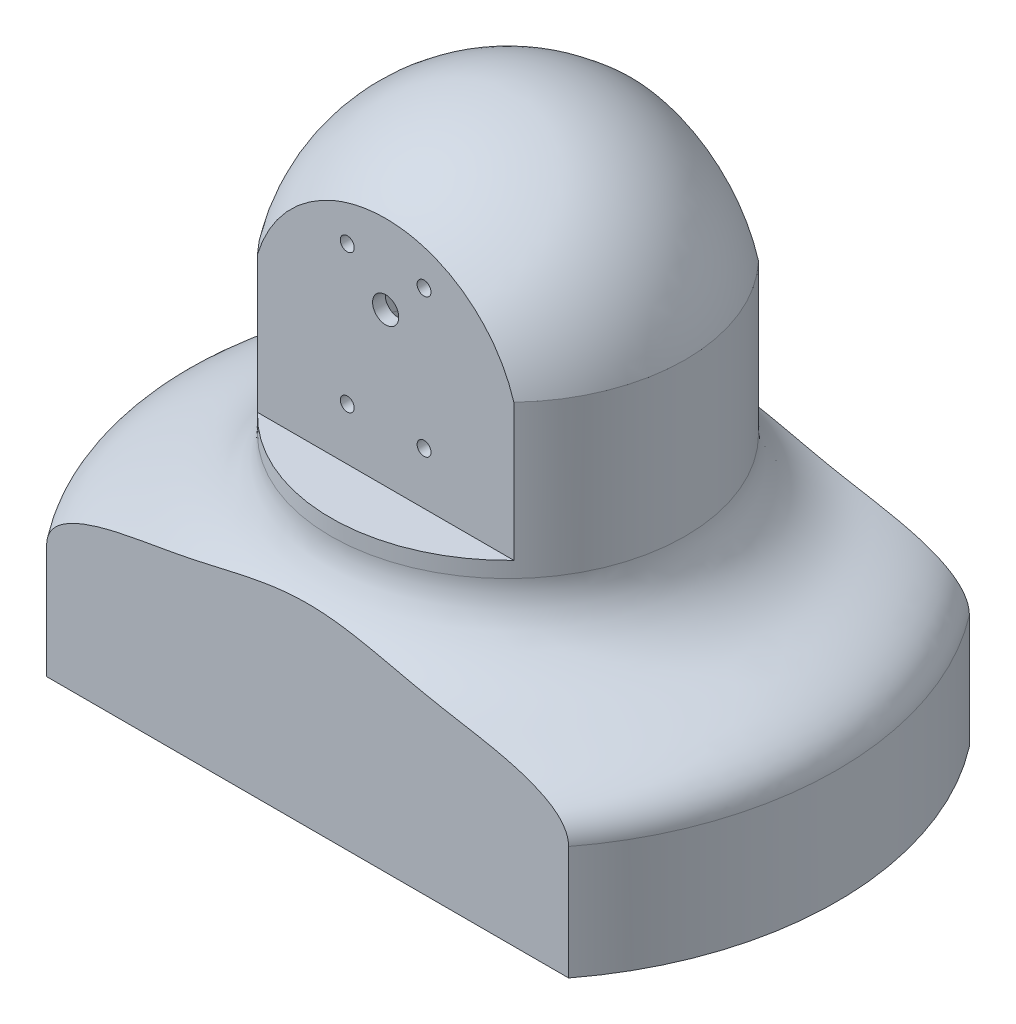
SolidWorks part; units mm, degrees
ref_plane "前视基准面" through (0, 0, 0) normal (0, 0, 1) x (1, 0, 0)
ref_plane "上视基准面" through (0, 0, 0) normal (0, 1, 0) x (1, 0, 0)
ref_plane "右视基准面" through (0, 0, 0) normal (1, 0, 0) x (0, 0, -1)
sketch "草图1" plane through (0, 0, 0) normal (0, 0, 1) x (1, 0, 0)
  line L0 (0, 0) -> (0, 70) construction
  line L2 (42, 36.2195) -> (42, 0)
  line L10 (78, -30) -> (78, -57)
  line L11 (40.3, 36.0333) -> (40.3, 0)
  line L12 (76.3, -30) -> (76.3, -57)
  line L13 (0, 70) -> (0, 68.3)
  line L14 (76.3, -57) -> (78, -57)
  arc A0 (0, 70) -> (42, 36.2195) centre (0, 27) cw
  arc A3 (0, 68.3) -> (40.3, 36.0333) centre (0, 27) cw
  spline S0 degree 3 poles (78, -30) (78, -23.3742) (65.6712, -18.6568) (51.2973, -15.3356) (42, -7.2858) (42, 0) knots 0 0 0 0 0.385389 0.593507 1 1 1 1
  spline S1 degree 1 poles (76.3, -30) (40.3, 0) knots 0 0 1 1 construction
  spline S2 degree 3 poles (40.3, 0) (40.3, -0.6228) (40.3823, -1.8829) (40.851, -4.2563) (41.9515, -7.0083) (43.9043, -9.9015) (47.1183, -13.2234) (50.9478, -15.7672) (54.8412, -17.519) (58.657, -18.8118) (63.4973, -20.0659) (68.9371, -21.9357) (72.5722, -23.9487) (74.3303, -25.4159) (75.3332, -26.6912) (75.8783, -27.6978) (76.1608, -28.599) (76.2792, -29.3716) (76.3, -29.7932) (76.3, -30) knots 0 0 0 0 0.03125 0.0625 0.125 0.1875 0.25 0.375 0.4375 0.5 0.625 0.75 0.8125 0.875 0.90625 0.9375 0.96875 0.984375 1 1 1 1
  point P10 (33.3, -0.85)
  point P11 (73.98, -31.36)
  dimension "D3" = 43
  dimension "D1" = 70
  dimension "D2" = 42
  dimension "D5" = 78
  dimension "D6" = 30
  dimension "D7" = 27
  dimension "D4" = 1.7
revolve "旋转1" add sketch "草图1" angle 360 about L0
sketch "草图6" plane through (0, 0, 0) normal (1, 0, 0) x (0, 0, -1)
  line L0 (42, 0) -> (42, 36.2195) construction
  line L1 (42, 3.749) -> (29, 3.749)
  line L2 (42, 3.749) -> (42, 58.749)
  line L3 (42, 58.749) -> (29, 58.749)
  line L4 (29, 3.749) -> (29, 58.749)
  line L5 (0, 0) -> (0, 35.0449) construction
  line L6 (-42, 58.749) -> (-29, 58.749)
  line L7 (-29, 3.749) -> (-29, 58.749)
  line L8 (-42, 3.749) -> (-29, 3.749)
  line L9 (-42, 3.749) -> (-42, 58.749)
  arc A0 (42, 36.2195) -> (-42, 36.2195) centre (0, 27) ccw construction
  dimension "D1" = 29
  dimension "D2" = 55
extrude "切除-拉伸3" cut sketch "草图6" against normal through all and the other way through all
sketch "草图7" plane through (0, 0, -29) normal (0, 0, -1) x (-1, 0, 0)
  line L0 (30.3809, 3.749) -> (30.3809, 36.2195) construction
  line L1 (-30.3809, 36.2195) -> (-30.3809, 3.749) construction
  line L2 (30.3809, 3.749) -> (30.3809, 36.2195)
  line L3 (-30.3809, 36.2195) -> (-30.3809, 3.749)
  line L4 (-30.3809, 3.749) -> (30.3809, 3.749)
  arc A0 (30.3809, 36.2195) -> (-30.3809, 36.2195) centre (0, 27) ccw construction
  arc A1 (30.3809, 36.2195) -> (-30.3809, 36.2195) centre (0, 27) ccw
extrude "凸台-拉伸3" add sketch "草图7" against normal blind 3 draft 24 draft outward yes
sketch "草图8" plane through (0, 3.749, 0) normal (0, 1, 0) x (1, 0, 0)
  line L1 (-32.9848, 26) -> (32.9848, 26)
  line L4 (-30.7911, 26) -> (30.7911, 26) construction
  arc A0 (30.3809, 29) -> (-30.3809, 29) centre (0, 0) ccw construction
  arc A1 (32.9848, 26) -> (-32.9848, 26) centre (0, 0) ccw
  arc A2 (-30.3809, 29) -> (-30.3809, -29) centre (0, 0) ccw construction
extrude "凸台-拉伸5" add sketch "草图8" against normal blind 2
mirror "镜向1" about plane through (0, 0, 0) normal (0, 0, 1) of "凸台-拉伸5", "凸台-拉伸3"
sketch "草图2" plane through (0, 0, 26) normal (0, 0, 1) x (1, 0, 0)
  line L1 (-9.1, 49) -> (9.1, 49) construction
  line L2 (-9.1, 49) -> (-9.1, 16.1) construction
  line L3 (-9.1, 16.1) -> (9.1, 16.1) construction
  line L4 (9.1, 49) -> (9.1, 16.1) construction
  line L5 (-16, 54.87) -> (16, 54.87) construction
  line L6 (-16, 54.87) -> (-16, 8.87) construction
  line L7 (-16, 8.87) -> (16, 8.87) construction
  line L8 (16, 54.87) -> (16, 8.87) construction
  circle A0 centre (0, 40) radius 3.1
  circle A6 centre (9.1, 49) radius 1.65
  circle A7 centre (-9.1, 49) radius 1.65
  circle A8 centre (-9.1, 16.1) radius 1.65
  circle A9 centre (9.1, 16.1) radius 1.65
  arc A10 (42, 36.2195) -> (-42, 36.2195) centre (0, 27) ccw construction
  point P6 (0, 54.87)
  point P7 (0, 49)
  dimension "D3" = 6.2
  dimension "D8" = 30
  dimension "D9" = 3.3
  dimension "D1" = 32.9
  dimension "D2" = 18.2
  dimension "D4" = 32
  dimension "D5" = 46
  dimension "D6" = 7.23
  dimension "D7" = 9
extrude "切除-拉伸4" cut sketch "草图2" along normal through all
sketch "草图9" plane through (0, 0, -29) normal (0, 0, 1) x (1, 0, 0)
  circle A2 centre (0, 40) radius 4.05
  dimension "D1" = 8.1
extrude "切除-拉伸6" cut sketch "草图9" along normal up to surface (3 mm away) up to face at (0, 24.655, -26)
sketch "草图12" plane through (0, 0, 0) normal (0, 1, 0) x (1, 0, 0)
  line L1 (-61.8688, 47.5) -> (61.8688, 47.5)
  line L2 (-61.8688, 47.5) -> (-61.8688, 80)
  line L3 (-61.8688, 80) -> (61.8688, 80)
  line L4 (61.8688, 47.5) -> (61.8688, 80)
  circle A0 centre (0, 0) radius 78 construction
  dimension "D2" = 2
  dimension "D1" = 47.5
extrude "切除-拉伸7" cut sketch "草图12" against normal through all
sketch "草图13" plane through (0, 0, -47.5) normal (0, 0, -1) x (-1, 0, 0)
  line L0 (-61.8688, -57) -> (-61.8688, -30) construction
  line L1 (61.8688, -57) -> (61.8688, -30) construction
  line L2 (-61.8688, -57) -> (-61.8688, -30)
  line L3 (61.8688, -57) -> (61.8688, -30)
  line L4 (-61.8688, -57) -> (61.8688, -57)
  spline S0 degree 3 poles (1061.8524, -30.5387) (-757.4661, -291.558) (81.6142, -84.0195) (61.269, -27.2442) (60.9178, -26.6293) (60.0514, -25.4965) (59.5514, -24.9967) (58.4724, -24.0909) (57.8871, -23.6815) (56.6856, -22.9434) (56.0678, -22.6129) (54.8091, -22.0047) (54.168, -21.7273) (52.2188, -20.9536) (50.8829, -20.5144) (48.1818, -19.7315) (46.8207, -19.3896) (44.0859, -18.7665) (42.7119, -18.4857) (38.5792, -17.6953) (35.8099, -17.2355) (31.6698, -16.4801) (30.2919, -16.2179) (27.5426, -15.6633) (26.1712, -15.3708) (22.0634, -14.462) (19.3329, -13.8181) (13.8519, -12.6254) (11.0985, -12.0769) (6.9689, -11.4896) (5.5915, -11.3332) (2.8346, -11.12) (1.4551, -11.0635) (-1.3064, -11.0596) (-2.6883, -11.1122) (-5.4544, -11.3193) (-6.8385, -11.4735) (-9.6085, -11.8628) (-10.9964, -12.098) (-13.7611, -12.6197) (-15.1382, -12.9058) (-19.262, -13.8017) (-22.0012, -14.4478) (-26.1217, -15.3601) (-27.4973, -15.6539) (-30.2547, -16.2107) (-31.6366, -16.4739) (-35.7886, -17.2319) (-38.5656, -17.6927) (-42.7111, -18.4855) (-44.0894, -18.7672) (-46.834, -19.3928) (-48.1988, -19.7359) (-50.9001, -20.5198) (-52.2411, -20.9612) (-54.1961, -21.739) (-54.8385, -22.0179) (-56.0986, -22.6288) (-56.7164, -22.9607) (-57.6161, -23.5158) (-57.9123, -23.7112) (-58.4873, -24.1215) (-58.7665, -24.3367) (-59.3048, -24.791) (-59.5639, -25.0302) (-60.0572, -25.5384) (-60.2897, -25.8062) (-60.7136, -26.3645) (-60.9062, -26.6561) (-61.1611, -27.1154) (-61.2404, -27.2722) (-61.3866, -27.5936) (-61.4539, -27.7593) (-84.3344, -91.9368) (1007.071, -362.5093) (-1061.7077, -47.2272) knots -1.287115 -1.287115 -1.287115 -1.287115 0.015625 0.015625 0.03125 0.03125 0.046875 0.046875 0.0625 0.0625 0.078125 0.078125 0.09375 0.09375 0.125 0.125 0.15625 0.15625 0.1875 0.1875 0.25 0.25 0.28125 0.28125 0.3125 0.3125 0.375 0.375 0.4375 0.4375 0.46875 0.46875 0.5 0.5 0.53125 0.53125 0.5625 0.5625 0.59375 0.59375 0.625 0.625 0.6875 0.6875 0.71875 0.71875 0.75 0.75 0.8125 0.8125 0.84375 0.84375 0.875 0.875 0.90625 0.90625 0.921875 0.921875 0.9375 0.9375 0.945312 0.945312 0.953125 0.953125 0.960937 0.960937 0.96875 0.96875 0.976562 0.976562 0.980469 0.980469 0.984375 0.984375 2.479572 2.479572 2.479572 2.479572 only from (61.8688, -30) to (-61.8688, -30) construction
  spline S1 degree 3 poles (61.8688, -30) (61.8688, -29.2846) (61.7513, -28.5899) (61.269, -27.2442) (60.9178, -26.6293) (60.0514, -25.4965) (59.5514, -24.9967) (58.4724, -24.0909) (57.8871, -23.6815) (56.6856, -22.9434) (56.0678, -22.6129) (54.8091, -22.0047) (54.168, -21.7273) (52.2188, -20.9536) (50.8829, -20.5144) (48.1818, -19.7315) (46.8207, -19.3896) (44.0859, -18.7665) (42.7119, -18.4857) (38.5792, -17.6953) (35.8099, -17.2355) (31.6698, -16.4801) (30.2919, -16.2179) (27.5426, -15.6633) (26.1712, -15.3708) (22.0634, -14.462) (19.3329, -13.8181) (13.8519, -12.6254) (11.0985, -12.0769) (6.9689, -11.4896) (5.5915, -11.3332) (2.8346, -11.12) (1.4551, -11.0635) (-1.3064, -11.0596) (-2.6883, -11.1122) (-5.4544, -11.3193) (-6.8385, -11.4735) (-9.6085, -11.8628) (-10.9964, -12.098) (-13.7611, -12.6197) (-15.1382, -12.9058) (-19.262, -13.8017) (-22.0012, -14.4478) (-26.1217, -15.3601) (-27.4973, -15.6539) (-30.2547, -16.2107) (-31.6366, -16.4739) (-35.7886, -17.2319) (-38.5656, -17.6927) (-42.7111, -18.4855) (-44.0894, -18.7672) (-46.834, -19.3928) (-48.1988, -19.7359) (-50.9001, -20.5198) (-52.2411, -20.9612) (-54.1961, -21.739) (-54.8385, -22.0179) (-56.0986, -22.6288) (-56.7164, -22.9607) (-57.6161, -23.5158) (-57.9123, -23.7112) (-58.4873, -24.1215) (-58.7665, -24.3367) (-59.3048, -24.791) (-59.5639, -25.0302) (-60.0572, -25.5384) (-60.2897, -25.8062) (-60.7136, -26.3645) (-60.9062, -26.6561) (-61.1611, -27.1154) (-61.2404, -27.2722) (-61.3866, -27.5936) (-61.4539, -27.7593) (-61.752, -28.5954) (-61.8688, -29.2869) (-61.8688, -30) knots 0 0 0 0 0.015625 0.015625 0.03125 0.03125 0.046875 0.046875 0.0625 0.0625 0.078125 0.078125 0.09375 0.09375 0.125 0.125 0.15625 0.15625 0.1875 0.1875 0.25 0.25 0.28125 0.28125 0.3125 0.3125 0.375 0.375 0.4375 0.4375 0.46875 0.46875 0.5 0.5 0.53125 0.53125 0.5625 0.5625 0.59375 0.59375 0.625 0.625 0.6875 0.6875 0.71875 0.71875 0.75 0.75 0.8125 0.8125 0.84375 0.84375 0.875 0.875 0.90625 0.90625 0.921875 0.921875 0.9375 0.9375 0.945312 0.945312 0.953125 0.953125 0.960937 0.960937 0.96875 0.96875 0.976562 0.976562 0.980469 0.980469 0.984375 0.984375 1 1 1 1
extrude "凸台-拉伸7" add sketch "草图13" against normal blind 2
mirror "镜向2" about plane through (0, 0, 0) normal (0, 0, 1) of "凸台-拉伸7", "切除-拉伸7"
ref_plane "基准面2" through (0, -52, 0) normal (0, -1, 0) x (-1, 0, 0)
sketch "草图14" plane through (0, -52, 0) normal (0, -1, 0) x (1, 0, 0)
  line L0 (0, 0) -> (0, -19.9006) construction
  line L1 (0, 0) -> (17.2749, 0) construction
  line L2 (-61.249, 45.5) -> (61.249, 45.5) construction
  circle A0 centre (-63, 28.5) radius 1.65
  arc A1 (-61.249, 45.5) -> (-61.249, -45.5) centre (0, 0) ccw construction
  arc A2 (-64.5837, 40.628) -> (-73.1545, 21.6821) centre (0, 0) ccw
  arc A3 (-64.5837, 40.628) -> (-61.6777, 32.8013) centre (-60.1325, 37.8279) ccw
  arc A4 (-61.6777, 32.8013) -> (-65.3576, 24.667) centre (-63, 28.5) cw
  arc A5 (-65.3576, 24.667) -> (-73.1545, 21.6821) centre (-68.1126, 20.1878) ccw
  circle A6 centre (-63, -28.5) radius 1.65
  arc A7 (-64.5837, -40.628) -> (-61.6777, -32.8013) centre (-60.1325, -37.8279) cw
  arc A8 (-61.6777, -32.8013) -> (-65.3576, -24.667) centre (-63, -28.5) ccw
  arc A9 (-65.3576, -24.667) -> (-73.1545, -21.6821) centre (-68.1126, -20.1878) cw
  arc A10 (-64.5837, -40.628) -> (-73.1545, -21.6821) centre (0, 0) cw
  arc A11 (64.5837, 40.628) -> (61.6777, 32.8013) centre (60.1325, 37.8279) cw
  arc A12 (61.6777, 32.8013) -> (65.3576, 24.667) centre (63, 28.5) ccw
  arc A13 (65.3576, 24.667) -> (73.1545, 21.6821) centre (68.1126, 20.1878) cw
  arc A14 (64.5837, 40.628) -> (73.1545, 21.6821) centre (0, 0) cw
  circle A15 centre (63, 28.5) radius 1.65
  circle A16 centre (63, -28.5) radius 1.65
  arc A17 (64.5837, -40.628) -> (73.1545, -21.6821) centre (0, 0) ccw
  arc A18 (65.3576, -24.667) -> (73.1545, -21.6821) centre (68.1126, -20.1878) ccw
  arc A19 (61.6777, -32.8013) -> (65.3576, -24.667) centre (63, -28.5) cw
  arc A20 (64.5837, -40.628) -> (61.6777, -32.8013) centre (60.1325, -37.8279) ccw
  dimension "D1" = 4.5
  dimension "D2" = 3.3
  dimension "D3" = 63
  dimension "D5" = 5.2587
  dimension "D4" = 17
extrude "凸台-拉伸8" add sketch "草图14" against normal blind 5
chamfer "倒角1" distance 3 angle 45 4 edges at (69.5175, -47, 31.4484) (69.5175, -47, -31.4484) (-69.5175, -47, 31.4484) (-69.5175, -47, -31.4484)
sketch "草图15" plane through (0, -47, 0) normal (0, 1, 0) x (1, 0, 0)
  line L1 (-61.3834, -31.3) -> (-59.7668, -28.5)
  line L2 (-59.7668, -28.5) -> (-61.3834, -25.7)
  line L3 (-61.3834, -25.7) -> (-64.6166, -25.7)
  line L4 (-64.6166, -25.7) -> (-66.2332, -28.5)
  line L5 (-66.2332, -28.5) -> (-64.6166, -31.3)
  line L6 (-64.6166, -31.3) -> (-61.3834, -31.3)
  line L7 (-64.6166, 25.7) -> (-61.3834, 25.7)
  line L8 (-61.3834, 25.7) -> (-59.7668, 28.5)
  line L9 (-59.7668, 28.5) -> (-61.3834, 31.3)
  line L10 (-61.3834, 31.3) -> (-64.6166, 31.3)
  line L11 (-64.6166, 31.3) -> (-66.2332, 28.5)
  line L12 (-66.2332, 28.5) -> (-64.6166, 25.7)
  line L13 (64.6166, 25.7) -> (66.2332, 28.5)
  line L14 (66.2332, 28.5) -> (64.6166, 31.3)
  line L15 (64.6166, 31.3) -> (61.3834, 31.3)
  line L16 (61.3834, 31.3) -> (59.7668, 28.5)
  line L17 (59.7668, 28.5) -> (61.3834, 25.7)
  line L18 (61.3834, 25.7) -> (64.6166, 25.7)
  line L19 (64.6166, -31.3) -> (66.2332, -28.5)
  line L20 (66.2332, -28.5) -> (64.6166, -25.7)
  line L21 (64.6166, -25.7) -> (61.3834, -25.7)
  line L22 (61.3834, -25.7) -> (59.7668, -28.5)
  line L23 (59.7668, -28.5) -> (61.3834, -31.3)
  line L24 (61.3834, -31.3) -> (64.6166, -31.3)
  circle A0 centre (-63, -28.5) radius 2.8 construction
  circle A1 centre (-63, 28.5) radius 2.8 construction
  circle A2 centre (63, 28.5) radius 2.8 construction
  circle A3 centre (63, -28.5) radius 2.8 construction
  dimension "D1" = 5.6
extrude "切除-拉伸8" cut sketch "草图15" against normal blind 1
sketch "草图18" plane through (0, 3.749, 0) normal (0, 1, 0) x (1, 0, 0)
  line L0 (-30.3809, 29) -> (30.3809, 29)
  line L1 (-29.3939, 30) -> (29.3939, 30)
  circle A0 centre (0, 0) radius 42 construction
  arc A1 (30.3809, 29) -> (29.3939, 30) centre (0, 0) ccw
  arc A2 (-29.3939, 30) -> (-30.3809, 29) centre (0, 0) ccw
  dimension "D1" = 1
extrude "凸台-拉伸10" add sketch "草图18" along normal blind 17
sketch "草图19" plane through (0, 0, -30) normal (0, 0, -1) x (-1, 0, 0)
  line L0 (-22.3809, 15.749) -> (-12.8809, 15.749) construction
  line L1 (0, 0) -> (0, 27.9735) construction
  line L2 (-29.3939, 3.749) -> (29.3939, 3.749) construction
  line L3 (-30.3809, 36.2195) -> (-30.3809, 20.749) construction
  circle A0 centre (-12.8809, 15.749) radius 1.15
  circle A1 centre (-22.3809, 15.749) radius 1.15
  circle A2 centre (12.8809, 15.749) radius 1.15
  circle A3 centre (22.3809, 15.749) radius 1.15
  dimension "D1" = 2.3
  dimension "D2" = 9.5
  dimension "D3" = 12
  dimension "D4" = 8
extrude "切除-拉伸9" cut sketch "草图19" against normal up to surface (4 mm away) up to face at (-4.05, 40, -26)
sketch "草图20" plane through (0, 0, -26) normal (0, 0, 1) x (1, 0, 0)
  line L1 (21.1973, 17.799) -> (20.0138, 15.749)
  line L2 (20.0138, 15.749) -> (21.1973, 13.699)
  line L3 (21.1973, 13.699) -> (23.5645, 13.699)
  line L4 (23.5645, 13.699) -> (24.7481, 15.749)
  line L5 (24.7481, 15.749) -> (23.5645, 17.799)
  line L6 (23.5645, 17.799) -> (21.1973, 17.799)
  line L7 (11.6973, 17.799) -> (10.5138, 15.749)
  line L8 (10.5138, 15.749) -> (11.6973, 13.699)
  line L9 (11.6973, 13.699) -> (14.0645, 13.699)
  line L10 (14.0645, 13.699) -> (15.2481, 15.749)
  line L11 (15.2481, 15.749) -> (14.0645, 17.799)
  line L12 (14.0645, 17.799) -> (11.6973, 17.799)
  line L13 (-14.0645, 17.799) -> (-15.2481, 15.749)
  line L14 (-15.2481, 15.749) -> (-14.0645, 13.699)
  line L15 (-14.0645, 13.699) -> (-11.6973, 13.699)
  line L16 (-11.6973, 13.699) -> (-10.5138, 15.749)
  line L17 (-10.5138, 15.749) -> (-11.6973, 17.799)
  line L18 (-11.6973, 17.799) -> (-14.0645, 17.799)
  line L19 (-23.5645, 17.799) -> (-24.7481, 15.749)
  line L20 (-24.7481, 15.749) -> (-23.5645, 13.699)
  line L21 (-23.5645, 13.699) -> (-21.1973, 13.699)
  line L22 (-21.1973, 13.699) -> (-20.0138, 15.749)
  line L23 (-20.0138, 15.749) -> (-21.1973, 17.799)
  line L24 (-21.1973, 17.799) -> (-23.5645, 17.799)
  circle A0 centre (22.3809, 15.749) radius 2.05 construction
  circle A1 centre (12.8809, 15.749) radius 2.05 construction
  circle A2 centre (-12.8809, 15.749) radius 2.05 construction
  circle A3 centre (-22.3809, 15.749) radius 2.05 construction
  dimension "D1" = 4.1
extrude "切除-拉伸10" cut sketch "草图20" against normal offset from surface (2 mm away) 2 up to face at (-22.3809, 14.599, -30)
